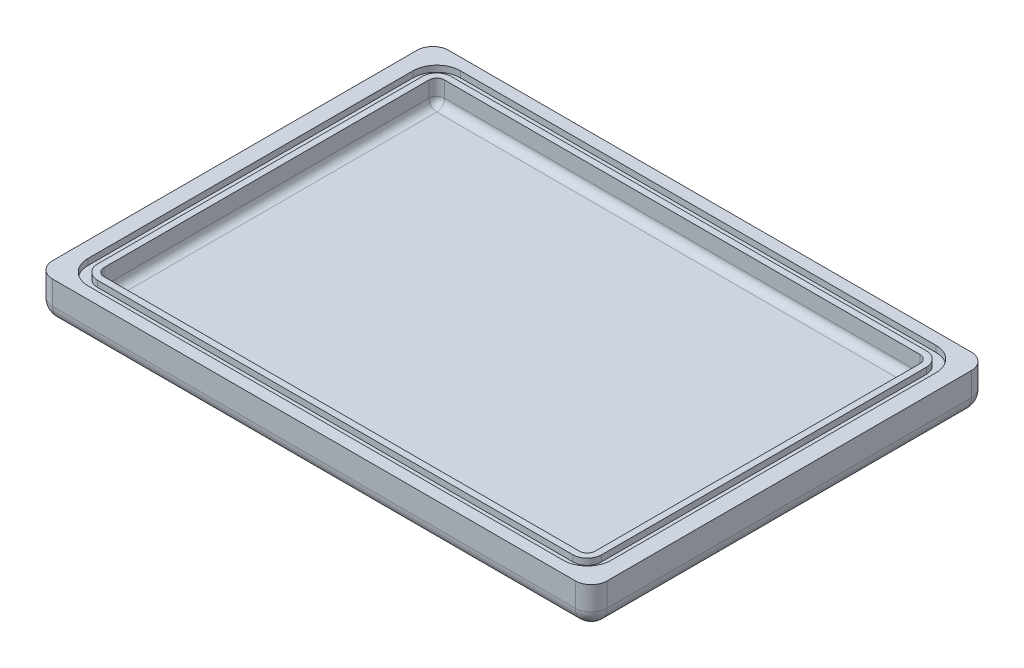
SolidWorks part; units mm, degrees
ref_plane "Front Plane" through (0, 0, 0) normal (0, 0, 1) x (1, 0, 0)
ref_plane "Top Plane" through (0, 0, 0) normal (0, 1, 0) x (1, 0, 0)
ref_plane "Right Plane" through (0, 0, 0) normal (1, 0, 0) x (0, 0, -1)
sketch "Sketch1" plane through (0, 0, 0) normal (0, 1, 0) x (1, 0, 0)
  line L1 (0, 0) -> (177.8, 0)
  line L2 (0, 0) -> (0, 127)
  line L3 (0, 127) -> (177.8, 127)
  line L4 (177.8, 0) -> (177.8, 127)
  dimension "D1" = 127
  dimension "D2" = 177.8
extrude "Boss-Extrude1" add sketch "Sketch1" along normal blind 12.7
fillet "Fillet1" radius 5.08 8 edges at (177.8, 0, -63.5) (88.9, 0, 0) (0, 0, -63.5) (88.9, 0, -127) (177.8, 6.35, -127) (0, 6.35, -127) (177.8, 6.35, 0) (0, 6.35, 0)
sketch "Sketch2" plane through (0, 12.7, 0) normal (0, 1, 0) x (1, 0, 0)
  line L0 (88.9, 127) -> (88.9, 0) construction
  line L1 (10.16, 8.89) -> (167.64, 8.89)
  line L2 (10.16, 8.89) -> (10.16, 118.11)
  line L3 (10.16, 118.11) -> (167.64, 118.11)
  line L4 (167.64, 8.89) -> (167.64, 118.11)
  line L5 (10.16, 8.89) -> (167.64, 118.11) construction
  line L6 (10.16, 118.11) -> (167.64, 8.89) construction
  line L7 (172.72, 127) -> (5.08, 127) construction
  line L8 (5.08, 0) -> (172.72, 0) construction
  point P0 (88.9, 63.5)
  point P11 (88.9, 63.5)
  dimension "D1" = 109.22
  dimension "D2" = 157.48
extrude "Cut-Extrude1" cut sketch "Sketch2" against normal blind 7.62
fillet "Fillet2" radius 2.54 8 edges at (88.9, 5.08, -118.11) (167.64, 5.08, -63.5) (88.9, 5.08, -8.89) (10.16, 5.08, -63.5) (10.16, 8.89, -8.89) (167.64, 8.89, -8.89) (167.64, 8.89, -118.11) (10.16, 8.89, -118.11)
sketch "Sketch3" plane through (0, 12.7, 0) normal (0, 1, 0) x (1, 0, 0)
  line L4 (165.1, 123.2154) -> (12.7, 123.2154)
  line L5 (5.0546, 115.57) -> (5.0546, 11.43)
  line L6 (12.7, 3.7846) -> (165.1, 3.7846)
  line L7 (172.7454, 11.43) -> (172.7454, 115.57)
  line L8 (169.672, 11.43) -> (169.672, 115.57)
  line L9 (12.7, 6.858) -> (165.1, 6.858)
  line L10 (8.128, 115.57) -> (8.128, 11.43)
  line L11 (165.1, 120.142) -> (12.7, 120.142)
  line L12 (169.672, 11.43) -> (169.672, 115.57)
  line L13 (12.7, 6.858) -> (165.1, 6.858)
  line L14 (8.128, 115.57) -> (8.128, 11.43)
  line L15 (165.1, 120.142) -> (12.7, 120.142)
  arc A4 (12.7, 123.2154) -> (5.0546, 115.57) centre (12.7, 115.57) ccw
  arc A5 (5.0546, 11.43) -> (12.7, 3.7846) centre (12.7, 11.43) ccw
  arc A6 (165.1, 3.7846) -> (172.7454, 11.43) centre (165.1, 11.43) ccw
  arc A7 (172.7454, 115.57) -> (165.1, 123.2154) centre (165.1, 115.57) ccw
  arc A8 (169.672, 115.57) -> (165.1, 120.142) centre (165.1, 115.57) ccw
  arc A9 (165.1, 6.858) -> (169.672, 11.43) centre (165.1, 11.43) ccw
  arc A10 (8.128, 11.43) -> (12.7, 6.858) centre (12.7, 11.43) ccw
  arc A11 (12.7, 120.142) -> (8.128, 115.57) centre (12.7, 115.57) ccw
  arc A12 (169.672, 115.57) -> (165.1, 120.142) centre (165.1, 115.57) ccw
  arc A13 (165.1, 6.858) -> (169.672, 11.43) centre (165.1, 11.43) ccw
  arc A14 (8.128, 11.43) -> (12.7, 6.858) centre (12.7, 11.43) ccw
  arc A15 (12.7, 120.142) -> (8.128, 115.57) centre (12.7, 115.57) ccw
  dimension "D1" = 2.032
  dimension "D2" = 3.0734
extrude "Cut-Extrude2" cut sketch "Sketch3" against normal blind 1.9812
